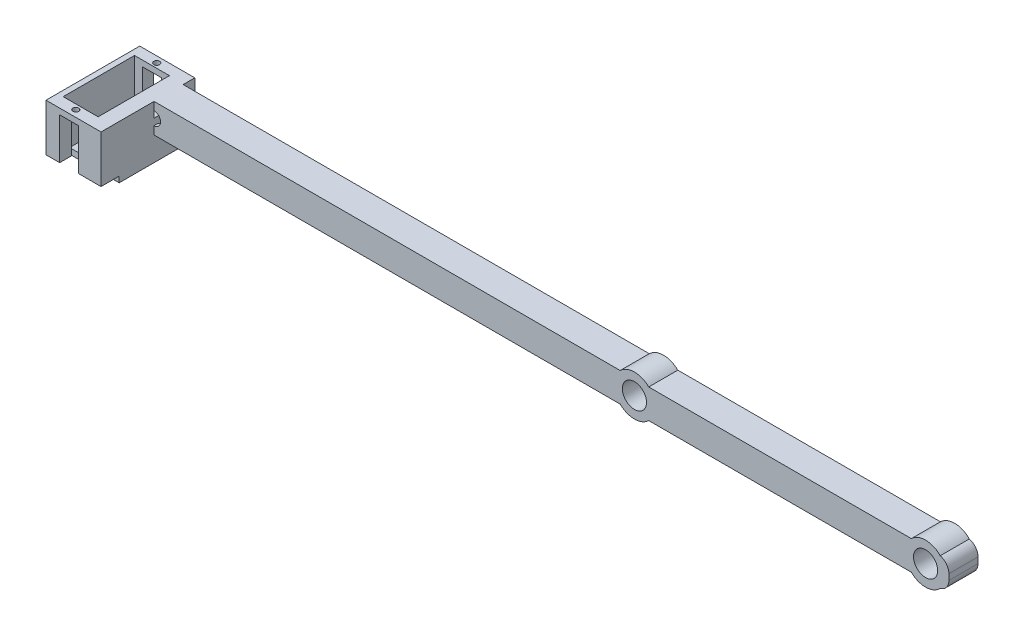
SolidWorks part; units mm, degrees
ref_plane "前视基准面" through (0, 0, 0) normal (0, 0, 1) x (1, 0, 0)
ref_plane "上视基准面" through (0, 0, 0) normal (0, 1, 0) x (1, 0, 0)
ref_plane "右视基准面" through (0, 0, 0) normal (1, 0, 0) x (0, 0, -1)
sketch "草图1" plane through (0, 0, 0) normal (0, 0, 1) x (1, 0, 0)
  line L9 (265, 5) -> (-5, 5)
  line L10 (265, -5) -> (-5, -5)
  line L11 (-5, -5) -> (-5, 5)
  arc A8 (265, -5) -> (265, 5) centre (265, 0) ccw
  circle A9 centre (0, 0) radius 2.25
  circle A10 centre (165, 0) radius 1.75
  circle A11 centre (265, 0) radius 1.75
  point P3 (94, 0.5349)
  dimension "D2" = 4.5
  dimension "D3" = 3.5
  dimension "D4" = 3.5
  dimension "D5" = 165
  dimension "D1" = 10
  dimension "D6" = 100
  dimension "D7" = 5
extrude "凸台-拉伸1" add sketch "草图1" against normal blind 10
sketch "草图2" plane through (0, 5, 0) normal (0, 1, 0) x (1, 0, 0)
  line L6 (265, 10) -> (265, 0) construction
  line L7 (-1.9771, 6.4282) -> (265, 6.4282)
  line L9 (-1.9771, 6.4282) -> (-1.9771, 2.1895)
  line L10 (-1.9771, 2.1895) -> (265, 2.1895)
  line L11 (265, 6.4282) -> (265, 2.1895)
sketch "草图3" plane through (-5, 0, 0) normal (-1, 0, 0) x (0, 0, 1)
  line L0 (0, -1.75) -> (0, 1.75) construction
  line L1 (-1.5, -3.5) -> (-8.5, -3.5)
  line L2 (-1.5, -3.5) -> (-1.5, 3.5)
  line L3 (-1.5, 3.5) -> (-8.5, 3.5)
  line L4 (-8.5, -3.5) -> (-8.5, 3.5)
  line L5 (-1.5, -3.5) -> (-8.5, 3.5) construction
  line L6 (-1.5, 3.5) -> (-8.5, -3.5) construction
  line L7 (-10, 5) -> (-10, -5) construction
  line L8 (-6.4282, 5) -> (-2.1895, 5) construction
  line L9 (-10, -5) -> (0, -5) construction
  point P0 (-5, 0)
  dimension "D1" = 1.5
  dimension "D2" = 1.5
  dimension "D3" = 1.5
  dimension "D4" = 1.5
extrude "切除-拉伸1" cut sketch "草图3" against normal through all
sketch "草图5" plane through (0, 0, -10) normal (0, 0, -1) x (-1, 0, 0)
  line L0 (5, 5) -> (18.9, 5)
  line L8 (-265, 5) -> (5, 5) construction
  line L9 (0, 5) -> (5, 5)
  line L13 (0, 0) -> (18.9, 0)
  line L14 (18.9, 0) -> (18.9, 5)
  line L15 (0, 0) -> (0, 5)
  line L16 (16.9, -6.4) -> (16.9, 4.5) construction
  dimension "D1" = 2
extrude "凸台-拉伸2" add sketch "草图5" along normal blind 4
sketch "草图7" plane through (0, 5, 0) normal (0, 1, 0) x (1, 0, 0)
  line L1 (-18.9, 10) -> (-5, 10) construction
  circle A0 centre (-10.95, 11.9) radius 1
  dimension "D1" = 1.9
extrude "切除-拉伸2" cut sketch "草图7" against normal blind 2
sketch "草图8" plane through (0, 0, 0) normal (0, -1, 0) x (1, 0, 0)
  line L0 (-14.2104, -14) -> (-14.2104, -10)
  line L1 (0, -14) -> (-18.9, -14) construction
  line L2 (-5, -10) -> (-18.9, -10) construction
  line L3 (-14.2104, -10) -> (-7.6935, -10)
  line L4 (-7.6935, -10) -> (-7.6935, -14)
  line L5 (-7.6935, -14) -> (-14.2104, -14)
extrude "切除-拉伸3" cut sketch "草图8" against normal blind 3
sketch "草图9" plane through (0, 0, -10) normal (0, 0, 1) x (1, 0, 0)
  line L0 (-18.9, 5) -> (-18.9, 0)
  line L1 (-18.9, 0) -> (-17, 0)
  line L6 (-17, 5) -> (-18.9, 5)
  line L8 (-17, 5) -> (-17, 0)
  line L9 (-16.9, 5) -> (-16.9, 4.5) construction
  dimension "D1" = 0.1
extrude "凸台-拉伸3" add sketch "草图9" along normal blind 24.5
sketch "草图10" plane through (0, 0, 0) normal (0, 0, 1) x (1, 0, 0)
  line L0 (-5, 0) -> (0, 0)
  line L1 (-5, -5) -> (-5, 5) construction
  line L2 (0, 0) -> (0, 5)
  line L3 (265, 5) -> (-5, 5) construction
  line L4 (0, 5) -> (-5, 5)
  line L5 (-5, 5) -> (-5, 0)
extrude "凸台-拉伸4" add sketch "草图10" along normal blind 14.2
sketch "草图11" plane through (0, 0, 14.2) normal (0, 0, 1) x (1, 0, 0)
  line L0 (0, 0) -> (-7.6935, 0)
  line L2 (-7.6935, 0) -> (-7.6935, 3)
  line L3 (-7.6935, 3) -> (-7.6935, 0) construction
  line L4 (-7.6935, 3) -> (-14.2104, 3)
  line L5 (-14.2104, 3) -> (-14.2104, 0)
  line L6 (-14.2104, 0) -> (-18.9, 0)
  line L7 (-18.9, 0) -> (-18.9, 5)
  line L8 (-18.9, 5) -> (0, 5)
  line L9 (0, 5) -> (0, 0)
extrude "凸台-拉伸9" add sketch "草图11" along normal blind 4
sketch "草图12" plane through (0, 5, 0) normal (0, 1, 0) x (1, 0, 0)
  line L0 (-5, -14.2) -> (-17, -14.2) construction
  circle A0 centre (-10.95, -15.9) radius 1
  dimension "D1" = 1.7
extrude "切除-拉伸4" cut sketch "草图12" against normal blind 3
sketch "草图13" plane through (0, 0, 0) normal (0, -1, 0) x (1, 0, 0)
  line L0 (-14.2104, -14) -> (-14.2104, -10)
  line L1 (-14.2104, -10) -> (-17, -10)
  line L2 (-17, -10) -> (-17, 14.2)
  line L3 (-17, 14.2) -> (-14.2104, 14.2)
  line L6 (-14.2104, 14.2) -> (-14.2104, 18.2)
  line L7 (-14.2104, 18.2) -> (-18.9, 18.2)
  line L8 (-18.9, 18.2) -> (-14.2104, 18.2) construction
  line L9 (-18.9, 18.2) -> (-18.9, -14)
  line L10 (-18.9, -14) -> (-14.2104, -14)
  line L11 (-7.6935, -14) -> (0, -14)
  line L12 (0, -14) -> (0, -10)
  line L13 (0, -10) -> (0, 18.2)
  line L14 (0, 18.2) -> (0, 0) construction
  line L15 (0, 18.2) -> (-7.6935, 18.2)
  line L16 (-7.6935, 18.2) -> (-7.6935, 14.2)
  line L17 (-7.6935, 14.2) -> (-5, 14.2)
  line L18 (-5, 14.2) -> (-5, -10)
  line L19 (-5, -10) -> (-7.6935, -10)
  line L20 (-7.6935, -10) -> (-7.6935, -14)
extrude "凸台-拉伸10" add sketch "草图13" along normal up to surface (11.25 mm away)
sketch "草图14" plane through (0, -11.25, 0) normal (0, -1, 0) x (-1, 0, 0)
  line L0 (18.9, -18.2) -> (18.9, 14) construction
  line L1 (18.9, 8.7786) -> (0, 8.7786)
  line L2 (18.9, 8.7786) -> (18.9, -11.9672)
  line L3 (18.9, -11.9672) -> (0, -11.9672)
  line L4 (0, 8.7786) -> (0, -11.9672)
  line L5 (0, 14) -> (0, -18.2) construction
extrude "凸台-拉伸13" add sketch "草图14" along normal blind 2
sketch "草图15" plane through (0, 5, 0) normal (0, 1, 0) x (1, 0, 0)
  line L0 (-17, 10) -> (-5, 10)
  line L1 (-5, 10) -> (-5, 10.3)
  line L2 (-5, 10.3) -> (-17, 10.3)
  line L3 (-17, 10.3) -> (-17, 10)
  dimension "D1" = 0.3
extrude "切除-拉伸5" cut sketch "草图15" against normal through all
sketch "草图16" plane through (0, 0, 0) normal (0, 0, 1) x (1, 0, 0)
  line L0 (265, 5) -> (-5, 5) construction
  line L1 (157, 5) -> (173, 5)
  line L2 (157, 5) -> (157, -5)
  line L3 (157, -5) -> (173, -5)
  line L4 (173, 5) -> (173, -5)
  line L5 (265, -5) -> (-5, -5) construction
  line L7 (257, 5) -> (273, 5)
  line L8 (257, 5) -> (257, -5)
  line L9 (257, -5) -> (273, -5)
  line L10 (273, 5) -> (273, -5)
  dimension "D1" = 16
  dimension "D2" = 8
  dimension "D3" = 16
  dimension "D4" = 8
extrude "凸台-拉伸14" add sketch "草图16" against normal blind 10
sketch "草图17" plane through (0, 0, 0) normal (0, 0, 1) x (1, 0, 0)
  circle A0 centre (165, 0) radius 4.04
  circle A1 centre (265, 0) radius 4.04
  dimension "D1" = 8.08
  dimension "D2" = 8.08
fillet "圆角1" radius 4 2 edges at (273, -5, -5) (273, 5, -5)
sketch "草图18" plane through (0, 0, 0) normal (0, 0, 1) x (1, 0, 0)
  circle A0 centre (165, 0) radius 6.5
  circle A1 centre (265, 0) radius 6.5
  dimension "D1" = 13
  dimension "D2" = 13
extrude "切除-拉伸7" cut sketch "草图17" against normal blind 10 contours A1 | A0
sketch "草图20" plane through (0, 0, 0) normal (0, 0, 1) x (1, 0, 0)
  circle A0 centre (165, 0) radius 4.04
  circle A1 centre (165, 0) radius 7
  circle A2 centre (265, 0) radius 4.04
  circle A3 centre (265, 0) radius 7
  dimension "D1" = 14
  dimension "D2" = 14
extrude "凸台-拉伸15" add sketch "草图20" against normal blind 10
fillet "圆角3" radius 3.5 2 edges at (76, 3.5, -8.5) (76, 3.5, -1.5)
sketch "草图21" plane through (0, 0, 0) normal (0, 0, 1) x (1, 0, 0)
  circle A0 centre (165, 0) radius 4.15
  circle A1 centre (265, 0) radius 4.15
  dimension "D1" = 8.3
  dimension "D2" = 8.3
extrude "切除-拉伸8" cut sketch "草图21" against normal blind 10
